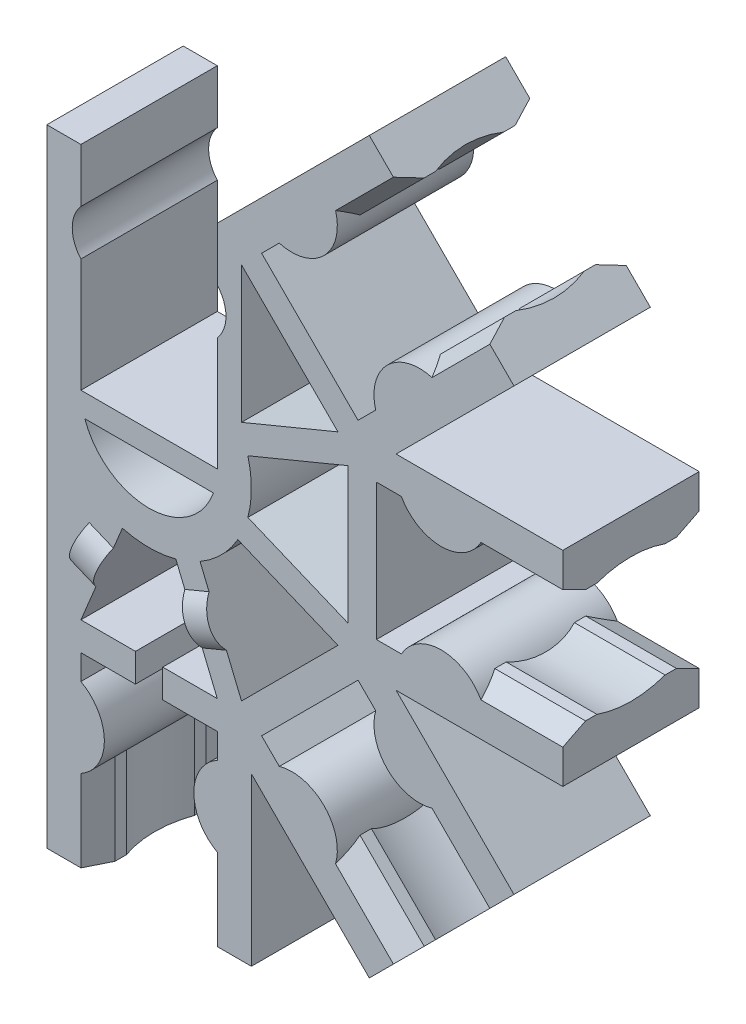
SolidWorks part; units mm, degrees
ref_plane "前视基准面" through (0, 0, 0) normal (0, 0, 1) x (1, 0, 0)
ref_plane "上视基准面" through (0, 0, 0) normal (0, 1, 0) x (1, 0, 0)
ref_plane "右视基准面" through (0, 0, 0) normal (1, 0, 0) x (0, 0, -1)
sketch "草图1" plane through (0, 0, 0) normal (0, 0, 1) x (1, 0, 0)
  line L0 (-4.5, 0) -> (-4.5, -18.2)
  line L1 (4.5, 0) -> (4.5, -18.2)
  line L2 (-4.5, -18.2) -> (-3, -18.2)
  line L3 (-3, -18.2) -> (-3, -14.6)
  line L4 (4.5, -18.2) -> (3, -18.2)
  line L5 (3, -18.2) -> (3, -14.6)
  line L6 (-3, -11.1) -> (-3, -10)
  line L7 (-3, -10) -> (3, -10)
  line L8 (3, -10) -> (3, -11.1)
  arc A0 (4.5, 0) -> (-4.5, 0) centre (0, 0) ccw
  arc A1 (-3, -11.1) -> (-3, -14.6) centre (-3.9682, -12.85) cw
  arc A2 (3, -11.1) -> (3, -14.6) centre (3.9682, -12.85) ccw
  point P1 (0, 4.5)
  dimension "D1" = 9
  dimension "D10" = 14.5
  dimension "D11" = 2
  dimension "D12" = 2
  dimension "D2" = 18.2
  dimension "D3" = 18.2
  dimension "D4" = 1.5
  dimension "D5" = 1.5
  dimension "D6" = 1.1
  dimension "D7" = 1.1
  dimension "D8" = 3.5
  dimension "D9" = 3.5
extrude "凸台-拉伸1" add sketch "草图1" along normal blind 6
sketch "草图3" plane through (0, -18.2, 0) normal (0, -1, 0) x (1, 0, 0)
  line L0 (-3, 6) -> (-3, 0)
  line L1 (-3, 0) -> (-2.5, 1)
  line L2 (-2.5, 1) -> (-2.5, 1.5)
  line L3 (-3, 6) -> (-2.5, 5)
  line L4 (-2.5, 5) -> (-2.5, 4.5)
  line L5 (0, 0) -> (0, 6.4845) construction
  line L6 (3, 0) -> (2.5, 1)
  line L7 (2.5, 1) -> (2.5, 1.5)
  line L8 (2.5, 5) -> (2.5, 4.5)
  line L9 (3, 6) -> (2.5, 5)
  line L10 (3, 6) -> (3, 0)
  arc A0 (-2.5, 1.5) -> (-2.5, 4.5) centre (1.7426, 3) cw
  arc A1 (2.5, 1.5) -> (2.5, 4.5) centre (-1.7426, 3) ccw
  dimension "D7" = 4.5
  dimension "D1" = 0.5
  dimension "D2" = 0.5
  dimension "D3" = 0.5
  dimension "D4" = 0.5
  dimension "D5" = 1.5
  dimension "D6" = 1.5
extrude "凸台-拉伸2" add sketch "草图3" against normal up to next
ref_axis "Axis" through (0, 0, 0) along (0, 0, 1)
pattern_circular "阵列(圆周)1" count 5 every 45 about axis through (0, 0, 0) along (0, 0, 1) of "凸台-拉伸1", "凸台-拉伸2"
sketch "草图4" plane through (0, 0, 0) normal (0, 0, -1) x (-1, 0, 0)
  line L0 (-3, -8.75) -> (-1.1749, -4.3439)
  line L1 (-3, -8.75) -> (-0.6, -8.75)
  line L2 (3, -8.75) -> (1.1749, -4.3439)
  line L3 (0, 0) -> (-4.5, -10.864) construction
  line L4 (3, -10) -> (-3, -10) construction
  line L5 (0, 0) -> (-10.864, -4.5) construction
  line L6 (-4.0659, -8.3085) -> (-8.3085, -4.0659)
  line L7 (-4.9497, -9.1924) -> (-9.1924, -4.9497) construction
  line L8 (0, 0) -> (-7.0711, -7.0711) construction
  line L9 (-8.3085, -4.0659) -> (-3.9024, -2.2408)
  line L10 (-4.0659, -8.3085) -> (-2.2408, -3.9024)
  line L11 (0, 0) -> (-10, 0) construction
  line L12 (-10, -3) -> (-10, 3) construction
  line L13 (-8.75, 3) -> (-4.3439, 1.1749)
  line L14 (0, 0) -> (-10.864, 4.5) construction
  line L15 (-8.3085, 4.0659) -> (-4.0659, 2.3085)
  line L16 (-8.75, -3) -> (-4.3439, -1.1749)
  line L17 (-8.75, 3) -> (-8.75, -3)
  line L18 (-4.5, 10.864) -> (-3, 9.364)
  line L19 (-4.0659, 2.3085) -> (-4.0659, 8.3085)
  line L20 (-8.3085, 4.0659) -> (-4.0659, 8.3085)
  line L21 (0, 0) -> (-7.0711, 7.0711) construction
  line L22 (-3.1166, 9.2578) -> (-1.2915, 4.8517) [skipped]
  line L23 (-7.3592, 5.0152) -> (-2.9531, 3.1901) [skipped]
  line L24 (-8.472, 3.6713) -> (-4.0659, 1.8462) [skipped]
  line L25 (-9.1924, 4.9497) -> (-4.9497, 9.1924) construction
  line L26 (-8.472, -2.3287) -> (-8.472, 3.6713) [skipped]
  line L27 (-8.472, -2.3287) -> (-4.0659, -0.5037) [skipped]
  line L28 (-3, 9.364) -> (-3, 7)
  line L29 (-9.6874, 16.0513) -> (-4.5, 10.864) construction
  line L30 (3, 9.364) -> (3, 7)
  line L31 (3, 9.364) -> (4.5, 9.364)
  line L32 (4.5, 18.2) -> (4.5, -18.2) construction
  line L33 (0, 0) -> (-3, 0)
  line L34 (0, 0) -> (3, 0)
  line L35 (-2.8284, -1) -> (2.8284, -1)
  line L36 (0.6, -8.75) -> (3, -8.75)
  line L37 (-0.6, -8.75) -> (-0.6, -10)
  line L38 (-0.6, -10) -> (0.6, -10)
  line L39 (0.6, -8.75) -> (0.6, -10)
  line L40 (-4.5, 10.864) -> (-4.5, 18.2)
  line L41 (-4.5, 18.2) -> (4.5, 18.2)
  line L42 (4.5, 18.2) -> (4.5, 9.364)
  line L45 (-3, 5) -> (-3, 0)
  line L46 (0, 0) -> (0, 10) construction
  line L47 (-3, 10) -> (3, 10) construction
  line L48 (3, 5) -> (3, 0)
  arc A0 (-2.8284, -1) -> (2.8284, -1) centre (0, 0) ccw
  arc A1 (-4.3439, -1.1749) -> (-4.3439, 1.1749) centre (0, 0) cw
  arc A2 (1.1749, -4.3439) -> (-1.1749, -4.3439) centre (0, 0) cw
  arc A3 (-3.9024, -2.2408) -> (-2.2408, -3.9024) centre (0, 0) ccw
  arc A4 (-3, 5) -> (-3, 7) centre (-1.882, 6) cw
  arc A5 (3, 5) -> (3, 7) centre (1.882, 6) ccw
  point P3 (-6.1872, 6.1872)
  point P5 (-6.1872, -6.1872)
  point P7 (0, -8.75)
  point P41 (0.9493, 0)
  dimension "D1" = 6
  dimension "D2" = 4.5
  dimension "D15" = 1.5
  dimension "D3" = 1.2
  dimension "D4" = 1.25
  dimension "D5" = 6
  dimension "D6" = 1.25
  dimension "D8" = 6
  dimension "D9" = 1.25
  dimension "D10" = 6
  dimension "D11" = 1
  dimension "D12" = 0.6
  dimension "D13" = 5
  dimension "D14" = 2
  dimension "D7" = 3
extrude "切除-拉伸1" cut sketch "草图4" against normal through all
sketch "草图5" plane through (-0.5329, -0.2207, 0) normal (-0.9239, -0.3827, 0) x (0, 0, 1)
  line L0 (0, 10.3732) -> (0, -15.0925) construction
  line L1 (0, -7.5) -> (0, -5.5)
  line L2 (3, 0) -> (3, -8.1298) construction
  line L3 (0, -4.4629) -> (0, -9.232) construction
  line L4 (6, -7.5) -> (6, -5.5)
  arc A0 (0, -5.5) -> (0, -7.5) centre (1.118, -6.5) ccw
  arc A1 (6, -5.5) -> (6, -7.5) centre (4.882, -6.5) cw
  dimension "D1" = 5.5
  dimension "D3" = 1.5
  dimension "D2" = 2
  dimension "D4" = 3
extrude "凸台-拉伸3" add sketch "草图5" against normal up to surface (1.1537 mm away) up to face at (3.1533, -6.1055, 3)
sketch "草图7" plane through (0.5329, -0.2207, 0) normal (0.9239, -0.3827, 0) x (0, 0, -1)
  line L1 (0, -9.232) -> (0, -4.4629) construction
  line L2 (0, -7.5) -> (0, -5.5)
  line L3 (-3, -4.6323) -> (-3, -8.3624) construction
  line L4 (-6, -7.5) -> (-6, -5.5)
  arc A0 (0, -5.5) -> (0, -7.5) centre (-1.118, -6.5) cw
  arc A1 (-6, -5.5) -> (-6, -7.5) centre (-4.882, -6.5) ccw
  point P3 (0.382, -6.5)
  dimension "D1" = 1.5
  dimension "D3" = 5.5
  dimension "D2" = 2
  dimension "D4" = 3
extrude "凸台-拉伸4" add sketch "草图7" against normal blind 1.15
